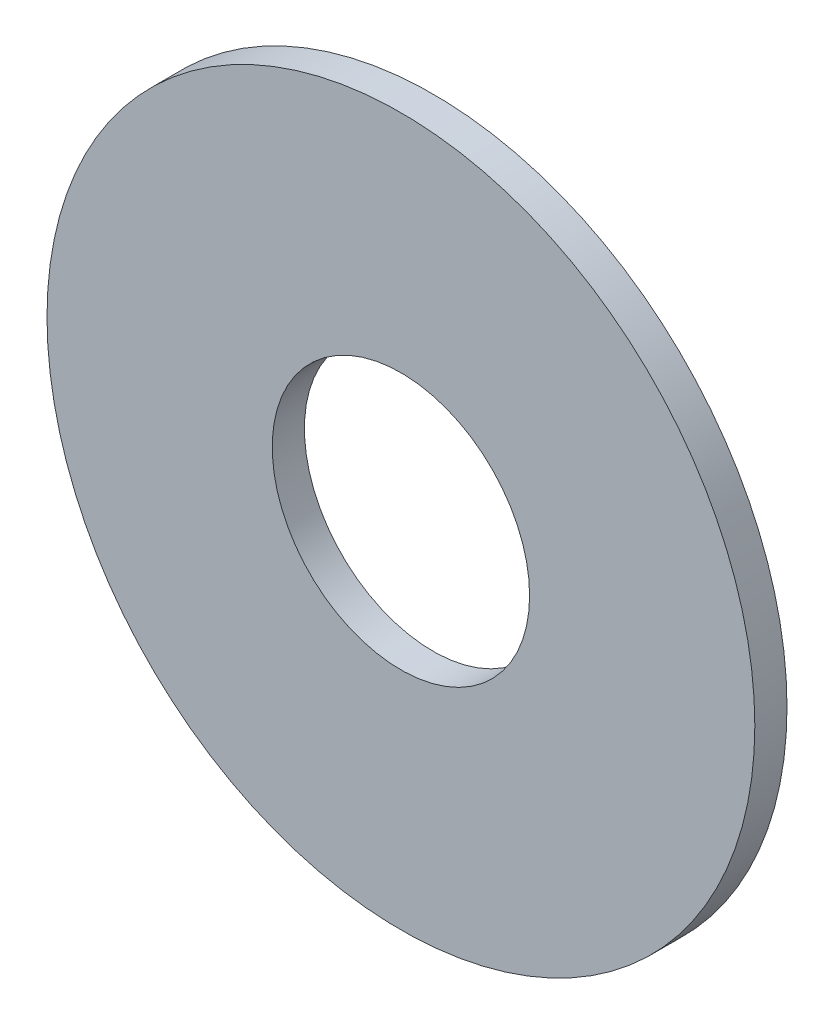
SolidWorks part; units mm, degrees
ref_plane "Front Plane" through (0, 0, 0) normal (0, 0, 1) x (1, 0, 0)
ref_plane "Top Plane" through (0, 0, 0) normal (0, 1, 0) x (1, 0, 0)
ref_plane "Right Plane" through (0, 0, 0) normal (1, 0, 0) x (0, 0, -1)
sketch "Sketch1" plane through (0, 0, 0) normal (0, 0, 1) x (1, 0, 0)
  circle A0 centre (0, 0) radius 5.5
  circle A1 centre (0, 0) radius 2
  circle A2 centre (0, 0) radius 17.526 construction
  circle A3 centre (17.526, 0) radius 1.651
  dimension "OD (d2)" = 11
  dimension "ID (d1)" = 4
  dimension "Circle Dia (d4)" = 35.052
  dimension "Hole Dia (d5)" = 3.302
sketch "Sketch2" plane through (0, 0, 0) normal (0, 0, 1) x (1, 0, 0)
  circle A0 centre (0, 0) radius 2 construction
  circle A1 centre (0, 0) radius 5.5 construction
  circle A2 centre (0, 0) radius 2
  circle A3 centre (0, 0) radius 5.5
extrude "Body Extrude" add sketch "Sketch2" along normal mid plane 0.5
sketch "Sketch3" plane through (0, 0, 0) normal (0, 0, 1) x (1, 0, 0)
  circle A0 centre (17.526, 0) radius 1.651 construction
  circle A1 centre (17.526, 0) radius 1.651
extrude "Hole Cut" [suppressed] cut sketch "Sketch3" against normal through all both and the other way through all
ref_axis "Center Axis 1" through (0, 0, 0.25) along (0, 0, -1)
ref_plane "Contact Plane 1" through (0, 0, -0.25) normal (0, 0, -1) x (-1, 0, 0)
